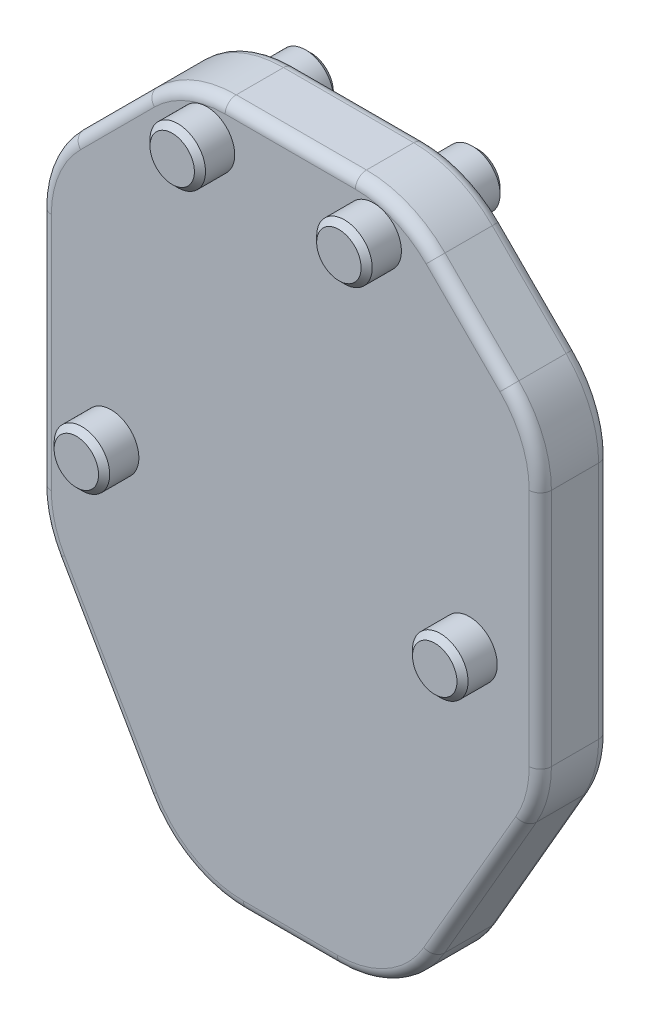
SolidWorks part; units mm, degrees
ref_plane "Ön Düzlem" through (0, 0, 0) normal (0, 0, 1) x (1, 0, 0)
ref_plane "Üst Düzlem" through (0, 0, 0) normal (0, 1, 0) x (1, 0, 0)
ref_plane "Sağ Düzlem" through (0, 0, 0) normal (1, 0, 0) x (0, 0, -1)
sketch "Çizim1" plane through (0, 0, 0) normal (0, 0, 1) x (1, 0, 0)
  line L0 (-40, 106.6987) -> (40, 106.6987)
  line L1 (40, 106.6987) -> (90, 56.6987)
  line L2 (90, 56.6987) -> (90, -56.6987)
  line L3 (90, -56.6987) -> (40, -143.3013)
  line L4 (40, -143.3013) -> (-40, -143.3013)
  line L5 (-40, -143.3013) -> (-90, -56.6987)
  line L6 (-90, -56.6987) -> (-90, 56.6987)
  line L7 (-90, 56.6987) -> (-40, 106.6987)
  point P8 (0, 106.6987)
  point P10 (90, 0)
  dimension "D1" = 135
  dimension "D2" = 80
  dimension "D3" = 120
  dimension "D4" = 250
  dimension "D5" = 50
extrude "Yükseklik-Ekstrüzyon1" add sketch "Çizim1" along normal mid plane 25
sketch "Çizim3" plane through (0, 0, 0) normal (0, 0, 1) x (1, 0, 0)
  line L0 (90, -56.6987) -> (90, 56.6987) construction
  line L1 (40, 106.6987) -> (-40, 106.6987) construction
  line L2 (0, 0) -> (0, 54.1138) construction
  circle A0 centre (30, 91.6987) radius 10
  circle A1 centre (64.5, -20) radius 10
  circle A2 centre (-64.5, -20) radius 10
  circle A3 centre (-30, 91.6987) radius 10
  dimension "D3" = 20
  dimension "D4" = 20
  dimension "D1" = 20
  dimension "D2" = 25.5
  dimension "D5" = 15
  dimension "D6" = 30
extrude "Yükseklik-Ekstrüzyon2" add sketch "Çizim3" along normal mid plane 50
sketch "Çizim4" plane through (0, 0, -12.5) normal (0, 0, -1) x (-1, 0, 0)
  line L0 (40, -143.3013) -> (-40, -143.3013) construction
  circle A0 centre (12.5, -113.3013) radius 10
  dimension "D1" = 20
  dimension "D2" = 30
  dimension "D3" = 12.5
extrude "Yükseklik-Ekstrüzyon3" add sketch "Çizim4" along normal blind 12.5
chamfer "Pah1" distance 2 angle 45 9 edges at (74.5, -20, 25) (-74.5, -20, 25) (-40, 91.6987, 25) (40, 91.6987, 25) (-40, 91.6987, -25) (40, 91.6987, -25) (-74.5, -20, -25) (-22.5, -113.3013, -25) (74.5, -20, -25)
fillet "Radyus1" radius 4 16 edges at (-65, 81.6987, 12.5) (-90, 0, 12.5) (0, -143.3013, 12.5) (-65, -100, 12.5) (0, 106.6987, 12.5) (65, -100, 12.5) (90, 0, 12.5) (65, 81.6987, 12.5) (-65, 81.6987, -12.5) (-90, 0, -12.5) (-65, -100, -12.5) (0, -143.3013, -12.5) (65, -100, -12.5) (90, 0, -12.5) (65, 81.6987, -12.5) (0, 106.6987, -12.5)
fillet "Radyus2" radius 40 24 edges at (39.5147, 105.5272, -11.3284) (39.5147, 105.5272, 11.3284) (88.8284, 56.2134, -11.3284) (88.8284, 56.2134, 11.3284) (88.8284, -56.3848, -11.3284) (88.8284, -56.3848, 11.3284) (39.3236, -142.1297, -11.3284) (39.3236, -142.1297, 11.3284) (-39.3236, -142.1297, -11.3284) (-39.3236, -142.1297, 11.3284) (-88.8284, -56.3848, -11.3284) (-88.8284, -56.3848, 11.3284) (-88.8284, 56.2134, -11.3284) (-88.8284, 56.2134, 11.3284) (-39.5147, 105.5272, -11.3284) (-39.5147, 105.5272, 11.3284) (-40, 106.6987, 0) (-90, 56.6987, 0) (-90, -56.6987, 0) (-40, -143.3013, 0) (40, -143.3013, 0) (90, -56.6987, 0) (90, 56.6987, 0) (40, 106.6987, 0)
